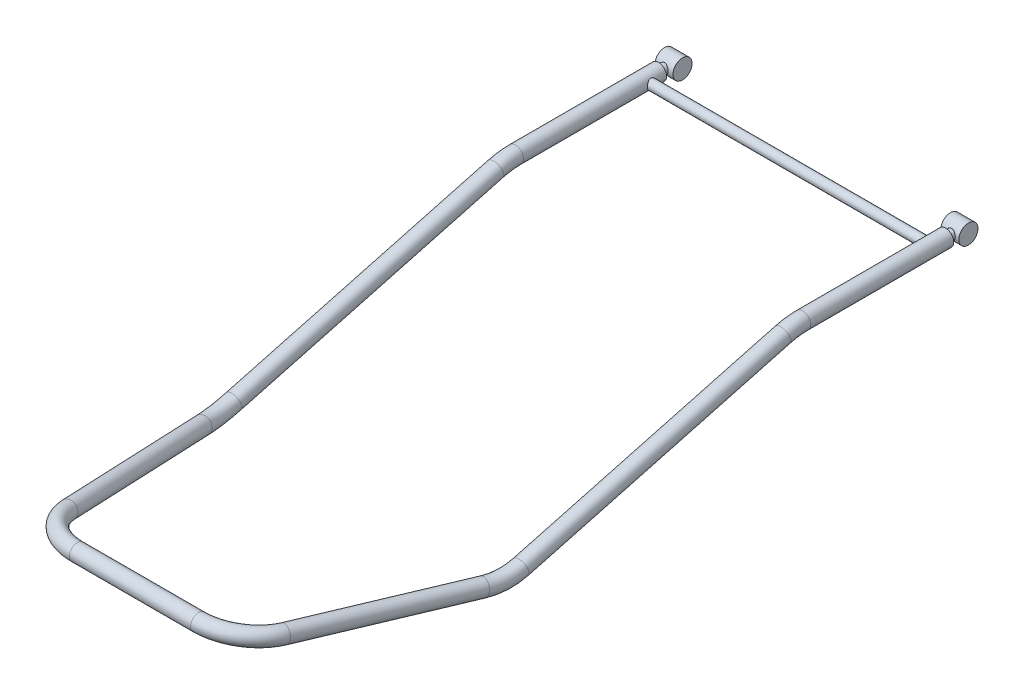
SolidWorks part; units mm, degrees
ref_plane "Front Plane" through (0, 0, 0) normal (0, 0, 1) x (1, 0, 0)
ref_plane "Top Plane" through (0, 0, 0) normal (0, 1, 0) x (1, 0, 0)
ref_plane "Right Plane" through (0, 0, 0) normal (1, 0, 0) x (0, 0, -1)
sketch "Sketch1" plane through (0, 0, 0) normal (1, 0, 0) x (0, 0, -1)
  line L0 (0, 0) -> (-222.25, 0) construction
  line L1 (-222.25, 0) -> (-605.6018, -102.7188) construction
  line L2 (-605.6018, -102.7188) -> (-900.3774, -56.0309) construction
  dimension "D1" = 222.25
  dimension "D2" = 165
  dimension "D3" = 396.875
  dimension "D4" = 156
  dimension "D5" = 298.45
sketch3d "3DSketch1"
  line L0 (0, 0, 0) -> (0, 0, 222.25) construction
  line L1 (0, 0, 222.25) -> (0, -102.7188, 605.6018) construction
  line L2 (0, -102.7188, 605.6018) -> (0, -56.0309, 900.3774) construction
  line L3 (0, 0, 0) -> (0, 0, 222.25) construction
  line L4 (0, 0, 222.25) -> (0, -102.7188, 605.6018) construction
  line L5 (0, -102.7188, 605.6018) -> (0, -56.0309, 900.3774) construction
  line L6 (0, 0, 0) -> (190.5, 0, 0) construction
  line L7 (190.5, 0, 0) -> (190.5, 0, 19.05)
  line L8 (190.5, 0, 19.05) -> (190.5, 0, 208.8741)
  line L9 (0, 0, 222.25) -> (190.5, 0, 222.25) construction
  line L10 (190.5, -3.4619, 235.1701) -> (190.5, -96.5902, 582.7295)
  line L11 (190.5, -102.7188, 605.6018) -> (0, -102.7188, 605.6018) construction
  line L12 (0, -56.0309, 900.3774) -> (80.4355, -56.0309, 900.3774)
  line L13 (142.7827, -64.0803, 849.5558) -> (186.0084, -99.0818, 628.5649)
  line L14 (179.832, 0, 19.05) -> (201.168, 0, 19.05) construction
  line L15 (201.168, 0, 19.05) -> (201.168, 0, 222.25) construction
  line L16 (201.168, 0, 222.25) -> (190.5, 0, 222.25) construction
  line L17 (179.832, 0, 19.05) -> (179.832, 0, 222.25) construction
  line L18 (190.5, 0, 38.1) -> (0, 0, 38.1)
  line L19 (201.6125, 0, 0) -> (177.8, 0, 0)
  arc A0 (186.0084, -99.0818, 628.5649) -> (190.5, -96.5902, 582.7295) centre (146.9094, -7.9436, 606.4822) ccw
  arc A1 (190.5, 0, 208.8741) -> (190.5, -3.4619, 235.1701) centre (190.5, -101.6, 208.8741) ccw
  arc A2 (80.4355, -56.0309, 900.3774) -> (142.7827, -64.0803, 849.5558) centre (80.4355, -65.9645, 837.6592) ccw
  point P6 (190.5, 0, 38.1)
  point P12 (190.5, 0, 19.05)
  point P19 (190.5, -102.7188, 605.6018)
  point P21 (238.6831, 34.1617, 617.7643)
  point P24 (190.5, 0, 222.25)
  point P26 (292.1, -101.6, 208.8741)
  point P29 (132.842, -56.0309, 900.3774)
  point P30 (80.4355, -3.2463, 827.7256)
  point P33 (190.5, 0, 0)
  point P34 (199.2162, -7.1372, 7.5791)
  dimension "D3" = 21.336
  dimension "D7" = 101.6
  dimension "D8" = 63.5
  dimension "D1" = 222.25
  dimension "D2" = 19.05
  dimension "D4" = 38.1
  dimension "D6" = 132.842
  dimension "D9" = 23.8125
  dimension "D10" = 12.7
  dimension "D5" = 177.8
sweep "Main Frame" add path "3DSketch1" circular profile diameter 21.336 parameters "D3"=21.336
sweep "Cross Bar Bottom" add path "3DSketch1<3>" circular profile diameter 12.7 parameters "D3"=12.7
sketch3d "3DSketch1<3>" same geometry as "3DSketch1"
sweep "Swivel Connection" add path "3DSketch1<4>" circular profile diameter 12.7 parameters "D3"=12.7
sketch3d "3DSketch1<4>" same geometry as "3DSketch1"
sweep "Swivel Outer" add path "3DSketch1<5>" circular profile diameter 25.4 parameters "D3"=25.4
sketch3d "3DSketch1<5>" same geometry as "3DSketch1"
mirror "Mirror1" about plane through (0, 0, 0) normal (1, 0, 0) of "Main Frame", "Cross Bar Bottom", "Swivel Connection", "Swivel Outer"
equation "\"bar_dia\"= 0.84in"
equation "\"thin_bar_dia\"= 0.5in"
equation "\"D3@3DSketch1\"=\"bar_dia\""
equation "\"main_fillet\" = 4in"
equation "\"top_fillet\"= 2.5in"
equation "\"D8@3DSketch1\"=\"top_fillet\""
equation "\"D7@3DSketch1\"=\"main_fillet\""
equation "\"D3@Main Frame\"=\"bar_dia\""
equation "\"D3@Cross Bar Bottom\"=\"thin_bar_dia\""
equation "\"D3@Swivel Connection\"=\"thin_bar_dia\""
equation "\"D5@3DSketch1\"=14/2"
equation "\"swivel_major_dia\"= 1in"
equation "\"D3@Swivel Outer\"=\"swivel_major_dia\""
